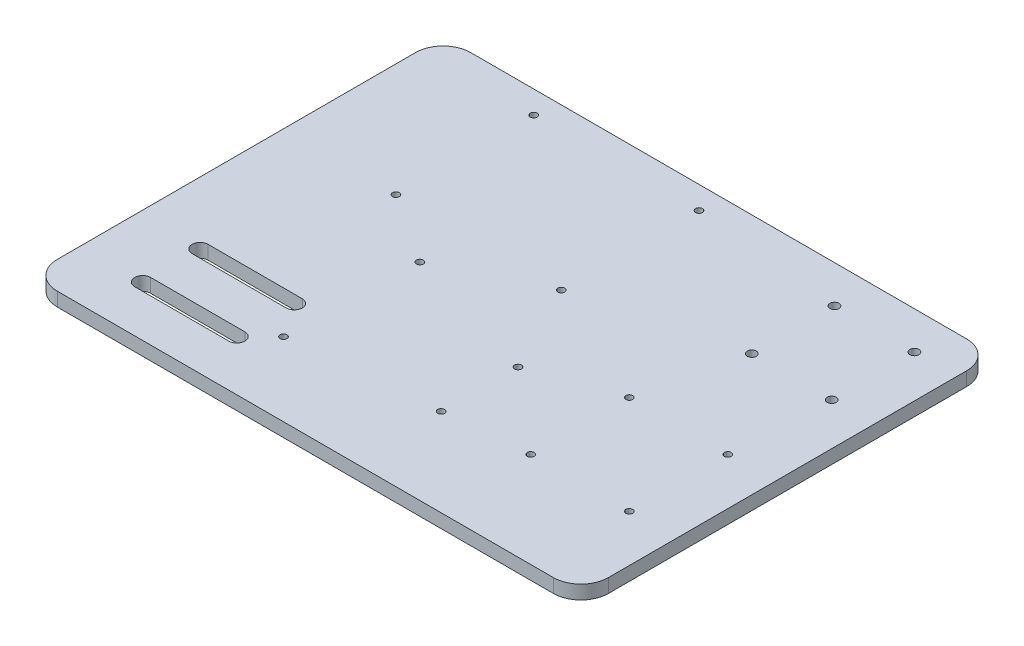
SolidWorks part; units mm, degrees
ref_plane "Front Plane" through (0, 0, 0) normal (0, 0, 1) x (1, 0, 0)
ref_plane "Top Plane" through (0, 0, 0) normal (0, 1, 0) x (1, 0, 0)
ref_plane "Right Plane" through (0, 0, 0) normal (1, 0, 0) x (0, 0, -1)
sketch "Sketch1" plane through (0, 0, 0) normal (0, 1, 0) x (1, 0, 0)
  line L1 (-90, -75) -> (90, -75)
  line L2 (-100, -65) -> (-100, 65)
  line L3 (-90, 75) -> (90, 75)
  line L4 (100, -65) -> (100, 65)
  line L5 (-100, -75) -> (100, 75) construction
  line L6 (-100, 75) -> (100, -75) construction
  arc A0 (90, -75) -> (100, -65) centre (90, -65) ccw
  arc A1 (-90, -75) -> (-100, -65) centre (-90, -65) cw
  arc A2 (-100, 65) -> (-90, 75) centre (-90, 65) cw
  arc A3 (90, 75) -> (100, 65) centre (90, 65) cw
  point P1 (0, 0)
  dimension "D3" = 10
  dimension "D1" = 200
  dimension "D2" = 150
extrude "Boss-Extrude1" add sketch "Sketch1" along normal blind 5 contours L2 A2 L3 A3 L4 A0 L1 A1
hole_wizard "arduino uno holes" positions "Sketch3" profile "Sketch2" tap size "M3x0.5" standard "ANSI Metric" end condition through all
sketch "Sketch3" plane through (0, 5, 0) normal (0, 1, 0) x (1, 0, 0)
  point P0 (17.4269, -15.2498)
  point P2 (17.4269, -43.1498)
  point P4 (-33.3731, -0.0498)
  point P6 (-34.6731, -48.2498)
  dimension "D1" = 27.9
  dimension "D2" = 15.2
  dimension "D3" = 50.8
  dimension "D4" = 1.3
  dimension "D5" = 5.1
sketch "Sketch2" plane through (17.4269, 5, 15.2498) normal (1, 0, 0) x (0, 0, 1)
  line L0 (0, 0) -> (0, 5)
  line L1 (0, 5) -> (1.25, 5)
  line L2 (1.25, 5) -> (1.25, 0)
  line L5 (1.25, 0) -> (0, 0)
  line L11 (0, -6.35) -> (0, 107.95) construction
  dimension "Thru Tap Drill Dia." = 2.5
  dimension "Thru Tap Drill Depth" = 5
cosmetic thread "Hole Thread1" parameters "D2"=3
cosmetic thread "Hole Thread2" parameters "D2"=3
cosmetic thread "Hole Thread3" parameters "D2"=3
cosmetic thread "Hole Thread4" parameters "D2"=3
hole_wizard "l298n holes" positions "Sketch16" profile "Sketch17" tap size "M3x0.5" standard "ANSI Metric" end condition through all
sketch "Sketch16" plane through (0, 5, 0) normal (0, 1, 0) x (1, 0, 0)
  point P0 (47.2019, -40.4092)
  point P6 (82.9619, -40.4092)
  point P7 (82.9619, -4.6492)
  point P8 (47.2019, -4.6492)
  dimension "D1" = 2
  dimension "D2" = 2
sketch "Sketch17" plane through (47.2019, 5, 40.4092) normal (1, 0, 0) x (0, 0, 1)
  line L0 (0, 0) -> (0, 5)
  line L1 (0, 5) -> (1.25, 5)
  line L2 (1.25, 5) -> (1.25, 0)
  line L5 (1.25, 0) -> (0, 0)
  line L11 (0, -6.35) -> (0, 107.95) construction
  dimension "Thru Tap Drill Dia." = 2.5
  dimension "Thru Tap Drill Depth" = 5
cosmetic thread "Hole Thread25" parameters "D2"=3
cosmetic thread "Hole Thread26" parameters "D2"=3
cosmetic thread "Hole Thread27" parameters "D2"=3
cosmetic thread "Hole Thread28" parameters "D2"=3
hole_wizard "protoboard holes" positions "Sketch20" profile "Sketch21" tap size "M3x0.5" standard "ANSI Metric" end condition through all
sketch "Sketch20" plane through (0, 5, 0) normal (0, 1, 0) x (1, 0, 0)
  point P0 (-58.9099, 16.7748)
  point P6 (1.0901, 16.7748)
  point P7 (1.0901, 66.7748)
  point P8 (-58.9099, 66.7748)
  dimension "D1" = 2
  dimension "D2" = 2
sketch "Sketch21" plane through (-58.9099, 5, -16.7748) normal (1, 0, 0) x (0, 0, 1)
  line L0 (0, 0) -> (0, 5)
  line L1 (0, 5) -> (1.25, 5)
  line L2 (1.25, 5) -> (1.25, 0)
  line L5 (1.25, 0) -> (0, 0)
  line L11 (0, -6.35) -> (0, 107.95) construction
  dimension "Thru Tap Drill Dia." = 2.5
  dimension "Thru Tap Drill Depth" = 5
cosmetic thread "Hole Thread37" parameters "D2"=3
cosmetic thread "Hole Thread38" parameters "D2"=3
cosmetic thread "Hole Thread39" parameters "D2"=3
cosmetic thread "Hole Thread40" parameters "D2"=3
hole_wizard "l-bracket holes" positions "Sketch22" profile "Sketch23" tap size "M4x0.7" standard "ANSI Metric" end condition through all
sketch "Sketch22" plane through (0, 5, 0) normal (0, 1, 0) x (1, 0, 0)
  point P12 (55.6434, 61.3769)
  point P19 (84.6434, 61.3769)
  point P20 (84.6434, 31.3769)
  point P21 (55.6434, 31.3769)
  dimension "D1" = 2
  dimension "D2" = 2
sketch "Sketch23" plane through (55.6434, 5, -61.3769) normal (1, 0, 0) x (0, 0, 1)
  line L0 (0, 0) -> (0, 5)
  line L1 (0, 5) -> (1.65, 5)
  line L2 (1.65, 5) -> (1.65, 0)
  line L5 (1.65, 0) -> (0, 0)
  line L11 (0, -6.35) -> (0, 107.95) construction
  dimension "Thru Tap Drill Dia." = 3.3
  dimension "Thru Tap Drill Depth" = 5
cosmetic thread "Hole Thread41" parameters "D2"=4
cosmetic thread "Hole Thread42" parameters "D2"=4
cosmetic thread "Hole Thread43" parameters "D2"=4
cosmetic thread "Hole Thread44" parameters "D2"=4
sketch "Sketch24" plane through (0, 5, 0) normal (0, 1, 0) x (1, 0, 0)
  line L0 (-43.1873, -35.8328) -> (-77.3641, -35.8328) construction
  line L1 (-43.1873, -38.7445) -> (-77.3641, -38.7445)
  line L2 (-43.1873, -32.9212) -> (-77.3641, -32.9212)
  line L4 (-43.1873, -56.6561) -> (-77.3641, -56.6561) construction
  line L5 (-43.1873, -53.7445) -> (-77.3641, -53.7445)
  line L6 (-43.1873, -59.5677) -> (-77.3641, -59.5677)
  arc A0 (-43.1873, -38.7445) -> (-43.1873, -32.9212) centre (-43.1873, -35.8328) ccw
  arc A1 (-77.3641, -32.9212) -> (-77.3641, -38.7445) centre (-77.3641, -35.8328) ccw
  arc A2 (-43.1873, -53.7445) -> (-43.1873, -59.5677) centre (-43.1873, -56.6561) cw
  arc A3 (-77.3641, -59.5677) -> (-77.3641, -53.7445) centre (-77.3641, -56.6561) cw
  point P2 (-60.2757, -35.8328)
  point P7 (-80.2757, -35.8328)
  point P8 (-40.2757, -35.8328)
  point P11 (-60.2757, -56.6561)
  point P16 (-38.9863, -45.9861)
  point P17 (-38.9218, -46.2445)
  dimension "D1" = 15
  dimension "D2" = 40
extrude "Cut-Extrude1" cut sketch "Sketch24" against normal through all
equation "\"w\"= 200"
equation "\"D1@Sketch1\"=\"w\""
equation "\"h\"= 150"
equation "\"D2@Sketch1\"=\"h\""
equation "\"th\"=5"
equation "\"D1@Boss-Extrude1\"=\"th\""
